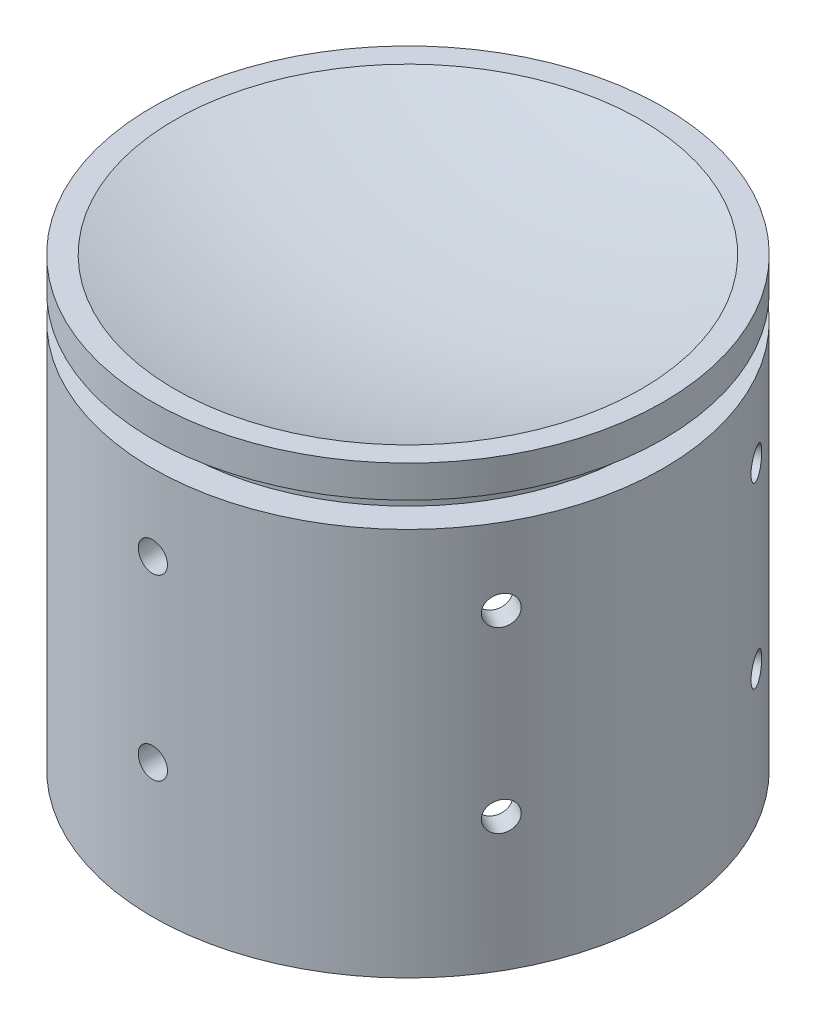
SolidWorks part; units mm, degrees
material "6061-T6 (SS)"
ref_plane "Front Plane" through (0, 0, 0) normal (0, 0, 1) x (1, 0, 0)
ref_plane "Top Plane" through (0, 0, 0) normal (0, 1, 0) x (1, 0, 0)
ref_plane "Right Plane" through (0, 0, 0) normal (1, 0, 0) x (0, 0, -1)
sketch "Sketch1" plane through (0, 0, 0) normal (0, 0, 1) x (1, 0, 0)
  line L0 (0, -25.4) -> (36.4236, -25.4)
  line L1 (0, 0) -> (36.4236, 0)
  line L2 (0, 0) -> (0, -63.5)
  line L3 (0, -63.5) -> (36.4236, -63.5)
  line L4 (36.4236, 0) -> (36.4236, -63.5)
  line L5 (36.3855, -25.4) -> (36.3855, 0)
  line L6 (0, -14.4216) -> (0, 22.2823) construction
  line L7 (33.2105, 0) -> (33.2105, -25.4)
  line L8 (36.3855, -25.4) -> (36.3855, -63.5)
  line L9 (0, 0) -> (0, -5.08)
  line L10 (0, -5.08) -> (0, -10.16)
  line L11 (0, -10.16) -> (36.3855, -10.16)
  line L12 (36.3855, -10.16) -> (36.3855, 0)
  line L13 (33.2105, -25.4) -> (33.2105, -63.5)
  line L14 (36.3855, -4.572) -> (32.3215, -4.572)
  line L15 (36.3855, -4.572) -> (36.3855, -8.1788)
  line L16 (36.3855, -8.1788) -> (32.3215, -8.1788)
  line L17 (32.3215, -4.572) -> (32.3215, -8.1788)
  arc A0 (0, -5.08) -> (33.2105, 0) centre (0, 106.0168) ccw
  point P22 (34.3535, -8.1788)
  dimension "D8" = 5.08
  dimension "D1" = 36.4236
  dimension "D2" = 63.5
  dimension "D3" = 25.4
  dimension "D5" = 3.175
  dimension "D6" = 4.572
  dimension "D7" = 5.08
  dimension "D9" = 4.064
  dimension "D10" = 3.6068
ref_axis "Axis1" through (0, 0, 0) along (0, -1, 0)
revolve "Revolve2" add sketch "Sketch1" angle 360 about L2 region at (34.798, -17.78, 0) region at (34.798, -44.45, 0) region at (18.4717, -6.6161, 0) region at (34.798, -9.1694, 0) region at (34.798, -2.286, 0) reverse direction yes
hole_wizard "#19 (0.164) Diameter Hole1" positions "3DSketch7" profile "Sketch8" hole size "#19" standard "ANSI Inch" end condition through all
sketch3d "3DSketch7"
  point P3 (0, -19.05, 36.3855)
  point P14 (0, -44.45, 36.3855)
sketch "Sketch8" plane through (0, -19.05, 36.3855) normal (1, 0, 0) x (0, -1, 0)
  line L0 (0, 0) -> (0, 72.771)
  line L1 (0, 72.771) -> (2.0828, 72.771)
  line L2 (2.0828, 72.771) -> (2.0828, 0)
  line L5 (2.0828, 0) -> (0, 0)
  line L11 (0, -6.35) -> (0, 107.95) construction
  dimension "Thru Hole Dia." = 4.1656
  dimension "Thru Hole Depth" = 72.771
pattern_circular "CirPattern2" count 6 every 60 about axis through (0, 0, 0) along (0, -1, 0) of "#19 (0.164) Diameter Hole1"
